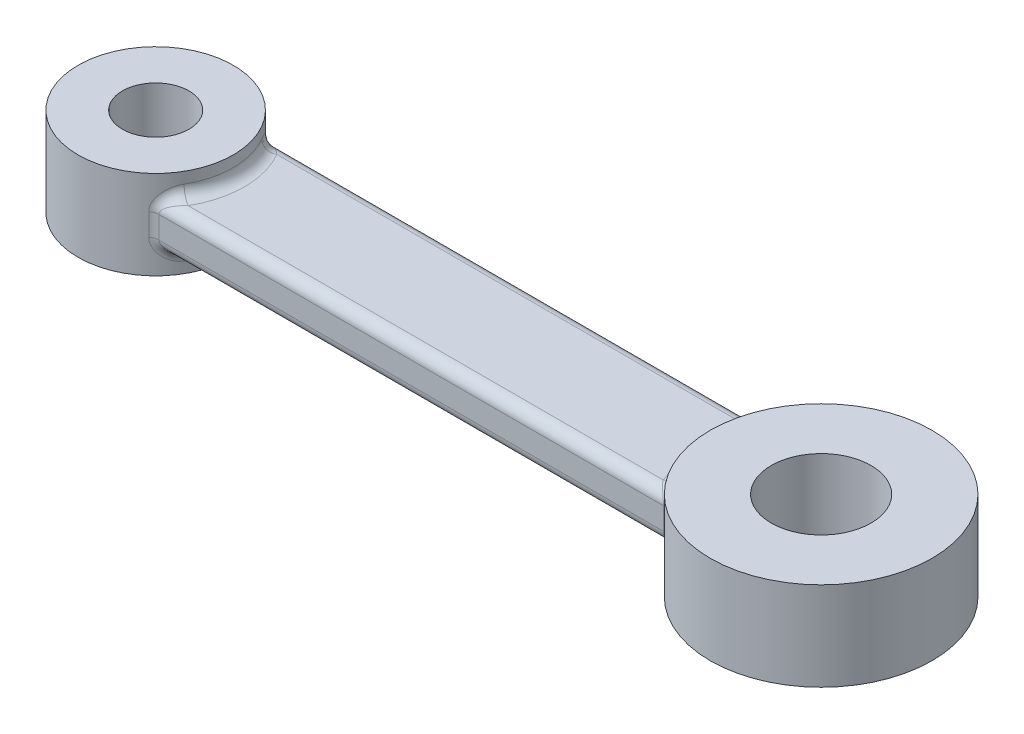
SolidWorks part; units mm, degrees
ref_plane "Front Plane" through (0, 0, 0) normal (0, 0, 1) x (1, 0, 0)
ref_plane "Top Plane" through (0, 0, 0) normal (0, 1, 0) x (1, 0, 0)
ref_plane "Right Plane" through (0, 0, 0) normal (1, 0, 0) x (0, 0, -1)
sketch "Sketch1" plane through (0, 0, 0) normal (0, 1, 0) x (1, 0, 0)
  line L1 (-15, -2.5) -> (15, -2.5)
  line L2 (-15, -2.5) -> (-15, 2.5)
  line L3 (-15, 2.5) -> (15, 2.5)
  line L4 (15, -2.5) -> (15, 2.5)
  line L5 (-15, -2.5) -> (15, 2.5) construction
  line L6 (-15, 2.5) -> (15, -2.5) construction
  point P0 (0, 0)
  dimension "D1" = 30
  dimension "D2" = 5
extrude "Boss-Extrude1" add sketch "Sketch1" along normal mid plane 2
sketch "Sketch3" plane through (0, 0, 0) normal (0, 1, 0) x (1, 0, 0)
  line L0 (15, -2.5) -> (15, 2.5) construction
  line L1 (-15, 2.5) -> (-15, -2.5) construction
  circle A0 centre (15, 0) radius 5
  circle A1 centre (-15, 0) radius 3.5
  dimension "D1" = 10
  dimension "D2" = 7
extrude "Boss-Extrude2" add sketch "Sketch3" along normal mid plane 4
sketch "Sketch4" plane through (0, 2, 0) normal (0, 1, 0) x (1, 0, 0)
  circle A0 centre (-15, 0) radius 1.5
  circle A1 centre (15, 0) radius 2.25
  dimension "D1" = 3
  dimension "D2" = 4.5
extrude "Cut-Extrude1" cut sketch "Sketch4" against normal through all
fillet "Fillet1" radius 0.5 4 edges at (-0.9403, -1, 2.5) (-0.9403, -1, -2.5) (-0.9403, 1, -2.5) (-0.9403, 1, 2.5)
fillet "Fillet2" radius 0.5 16 edges at (-12.4852, 0.7477, 2.4343) (-12.5505, 0, 2.5) (-12.4247, -0.8361, 2.3701) (-11.5, -1, 0) (-12.4852, -0.7477, -2.4343) (-12.5505, 0, -2.5) (-12.4247, 0.8361, -2.3701) (10.6204, 0.7829, -2.4123) (10.6699, 0, -2.5) (10.5801, -0.8688, -2.3376) (10, -1, 0) (10.6204, -0.7829, 2.4123) (10.6699, 0, 2.5) (10.5801, 0.8688, 2.3376) (-11.5, 1, 0) (10, 1, 0)
